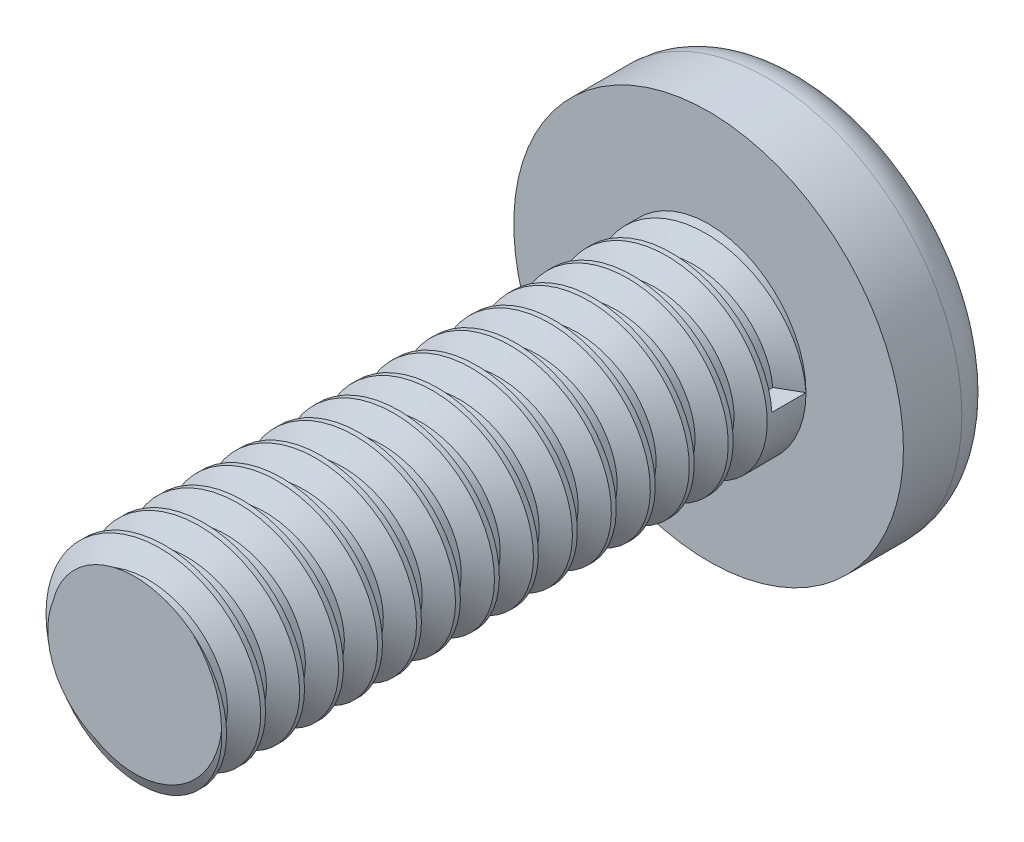
SolidWorks part; units mm, degrees
material "1.5810 (18NiCr5-4)"
ref_plane "Ebene vorne" through (0, 0, 0) normal (0, 0, 1) x (1, 0, 0)
ref_plane "Ebene oben" through (0, 0, 0) normal (0, 1, 0) x (1, 0, 0)
ref_plane "Ebene rechts" through (0, 0, 0) normal (1, 0, 0) x (0, 0, -1)
sketch "Skizze1" plane through (0, 0, 0) normal (0, 0, 1) x (1, 0, 0)
  circle A0 centre (0, 0) radius 10
  dimension "D1" = 20
extrude "Aufsatz-Linear austragen1" add sketch "Skizze1" along normal blind 5
sketch "Skizze2" plane through (0, 0, 5) normal (0, 0, 1) x (1, 0, 0)
  circle A0 centre (0, 0) radius 5
  dimension "D1" = 10
extrude "Aufsatz-Linear austragen2" add sketch "Skizze2" along normal blind 30
thread "Gewinde1" pitch 2 method cut profile "Gewindeprofil1" start angle 0, offset 0, length 30, pitch 2, diameter 10
ref_plane "Ebene1" through (5, 0, 5) normal (0, -1, 0) x (1, 0, 0)
sketch "Gewindeprofil1" plane through (5, 0, 5) normal (0, -1, 0) x (1, 0, 0)
  line L0 (0, 0) -> (0, 2) construction
  line L11 (0, 0) -> (0, 1.75)
  line L12 (0, 1.75) -> (-1.0825, 1.125)
  line L13 (-1.0825, 1.125) -> (-1.0825, 0.625)
  line L15 (-1.0825, 0.625) -> (0, 0)
  line L17 (-1.0825, 0.875) -> (0, 0.875) construction
  point P2 (0, 0)
  dimension "Pitch" = 2
  dimension "Profile_Angle" = 60
  dimension "Profile_Land" = 0.5
  dimension "Profile_Height" = 1.0825
fillet "Verrundung1" radius 2 1 edges at (10, 0, 0)
sketch "Skizze5" plane through (0, 0, 0) normal (0, 0, -1) x (-1, 0, 0)
  line L0 (0, 0) -> (6.1699, -5.0924) construction
  line L1 (0, 0) -> (31827.5163, 38561.7583) construction
  line L2 (-3.5379, 3.5684) -> (-0.0673, 0.7039)
  line L3 (-3.5379, 3.5684) -> (-4.1745, 2.7971)
  line L4 (4.1745, -2.7971) -> (3.5379, -3.5684)
  line L5 (-4.1745, 2.7971) -> (-0.7039, -0.0673)
  line L6 (3.5684, 3.5379) -> (2.7971, 4.1745)
  line L7 (3.5684, 3.5379) -> (0.7039, 0.0673)
  line L8 (2.7971, 4.1745) -> (-0.0673, 0.7039)
  line L9 (-2.7971, -4.1745) -> (-3.5684, -3.5379)
  line L10 (0.7039, 0.0673) -> (4.1745, -2.7971)
  line L11 (-0.7039, -0.0673) -> (-3.5684, -3.5379)
  line L12 (0.0673, -0.7039) -> (3.5379, -3.5684)
  line L13 (0.0673, -0.7039) -> (-2.7971, -4.1745)
  dimension "D1" = 1
  dimension "D2" = 1
  dimension "D3" = 0.5
  dimension "D4" = 0.5
  dimension "D5" = 10
  dimension "D6" = 10
  dimension "D7" = 5
  dimension "D8" = 5
extrude "Schnitt-Linear austragen1" cut sketch "Skizze5" against normal blind 1
